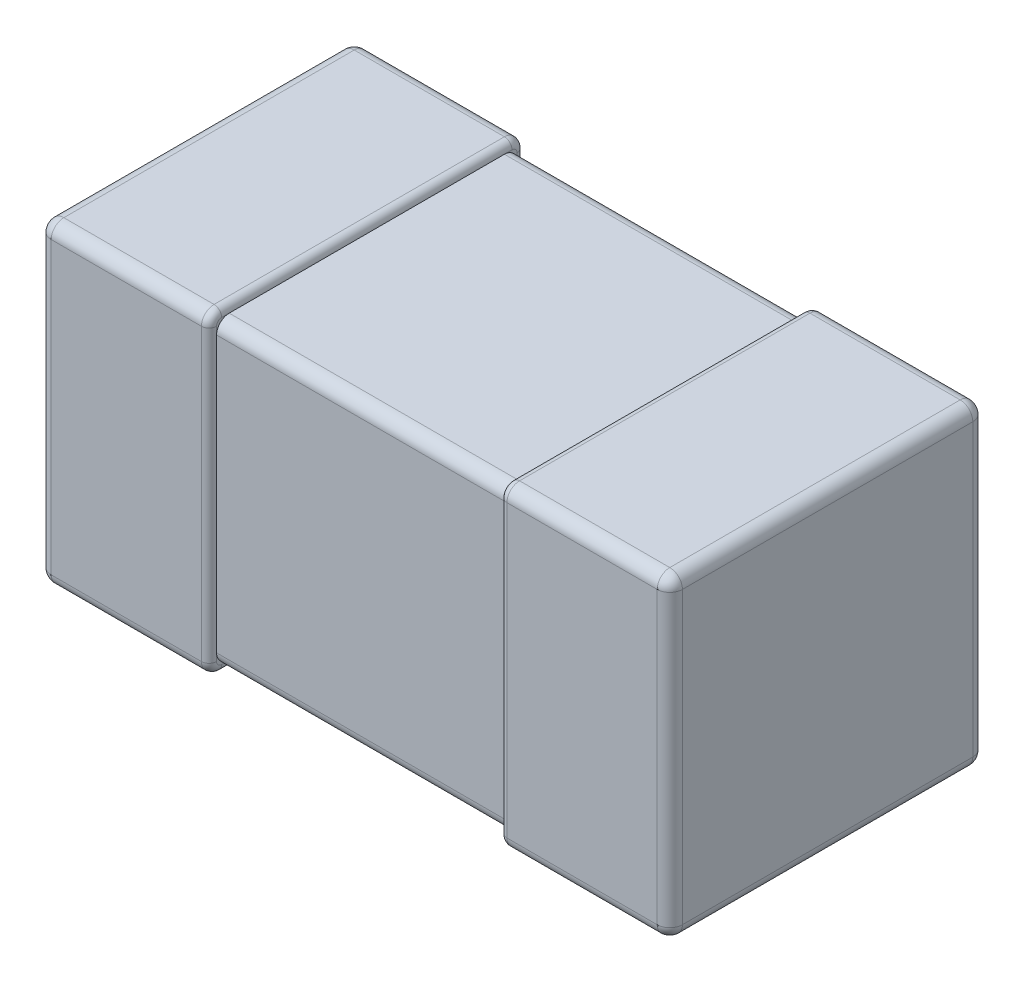
SolidWorks part; units mm, degrees
ref_plane "Top Plane" through (0, 0, 0) normal (0, 0, 1) x (1, 0, 0)
ref_plane "Front Plane" through (0, 0, 0) normal (0, 1, 0) x (1, 0, 0)
ref_plane "Side Plane" through (0, 0, 0) normal (1, 0, 0) x (0, 0, -1)
sketch "Sketch1" plane through (0, 0, 0) normal (0, 0, 1) x (1, 0, 0)
  line L1 (-0.125, 0.0625) -> (0.125, 0.0625)
  line L2 (-0.125, 0.0625) -> (-0.125, -0.0625)
  line L3 (-0.125, -0.0625) -> (0.125, -0.0625)
  line L4 (0.125, 0.0625) -> (0.125, -0.0625)
  dimension "D1" = 0.25
  dimension "D2" = 0.125
  dimension "D3" = 0.125
  dimension "D4" = 0.0625
extrude "All body" add sketch "Sketch1" along normal blind 0.125
sketch "Sketch2" plane through (0, 0, 0) normal (1, 0, 0) x (0, 0, -1)
  line L14 (-0.003, 0.0595) -> (-0.122, 0.0595)
  line L15 (-0.003, -0.0595) -> (-0.003, 0.0595)
  line L16 (-0.122, -0.0595) -> (-0.003, -0.0595)
  line L17 (-0.122, 0.0595) -> (-0.122, -0.0595)
  line L18 (-0.003, 0.0595) -> (-0.122, 0.0595)
  line L19 (-0.003, -0.0595) -> (-0.003, 0.0595)
  line L20 (-0.122, -0.0595) -> (-0.003, -0.0595)
  line L21 (-0.122, 0.0595) -> (-0.122, -0.0595)
  dimension "D1" = 0.003
extrude "Cut out the body for pin" cut sketch "Sketch2" against normal blind 0.0575 and the other way blind 0.0575 flip side to cut
fillet "Body fillet" radius 0.005 4 edges at (0, 0.0595, 0.003) (0, 0.0595, 0.122) (0, -0.0595, 0.003) (0, -0.0595, 0.122)
fillet "Pin fillet a" radius 0.005 16 edges at (0.125, -0.0625, 0.0625) (0.125, 0, 0.125) (0.125, 0.0625, 0.0625) (0.125, 0, 0) (-0.125, 0.0625, 0.0625) (-0.125, 0, 0.125) (-0.125, -0.0625, 0.0625) (-0.125, 0, 0) (0.0912, 0.0625, 0.125) (0.0913, -0.0625, 0.125) (0.0913, -0.0625, 0) (0.0912, 0.0625, 0) (-0.0912, 0.0625, 0) (-0.0912, -0.0625, 0) (-0.0912, 0.0625, 0.125) (-0.0912, -0.0625, 0.125)
fillet "Pin fillet b" radius 0.003 16 edges at (0.0575, -0.061, 0.1235) (0.0575, -0.0625, 0.0625) (0.0575, -0.061, 0.0015) (0.0575, 0, 0) (0.0575, 0.061, 0.0015) (0.0575, 0.0625, 0.0625) (0.0575, 0.061, 0.1235) (-0.0575, -0.061, 0.1235) (-0.0575, -0.0625, 0.0625) (-0.0575, -0.061, 0.0015) (-0.0575, 0, 0) (-0.0575, 0.061, 0.0015) (-0.0575, 0.0625, 0.0625) (-0.0575, 0.061, 0.1235) (0.0575, 0, 0.125) (-0.0575, 0, 0.125)
equation "\"D1@All body\"=\"Thickness\""
